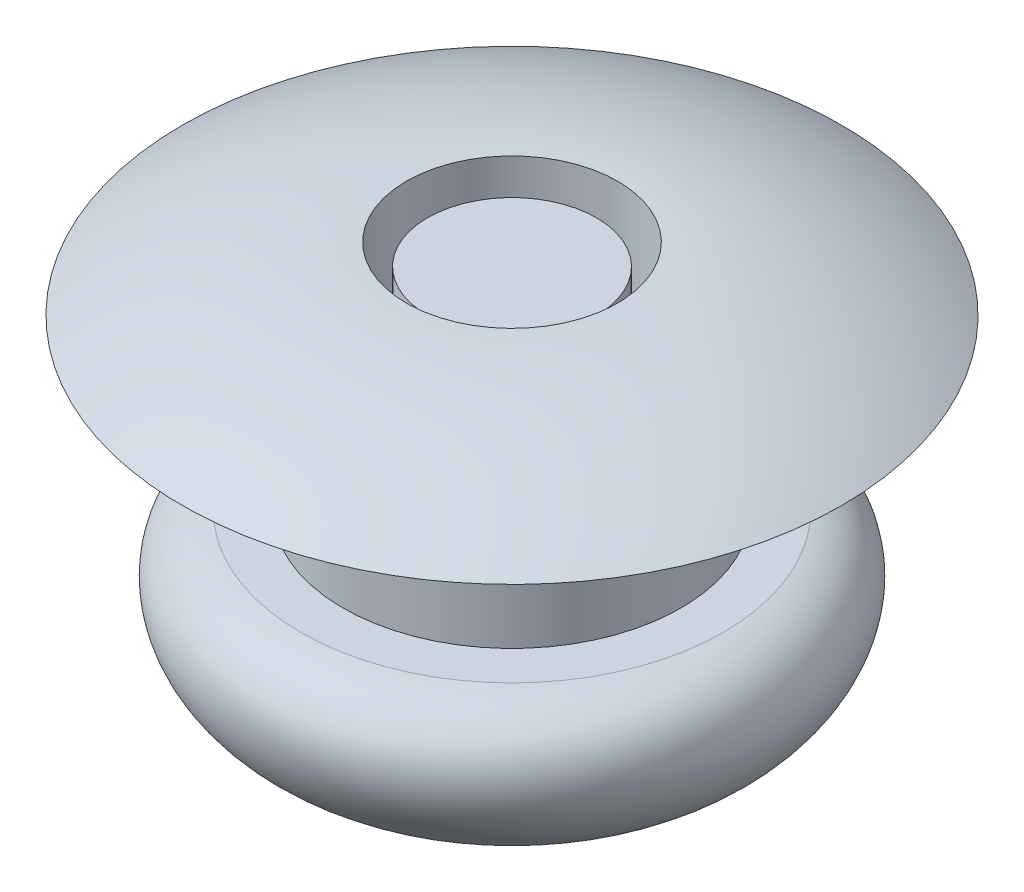
SolidWorks part; units mm, degrees
material "AISI 316 Arkusz stali nierdzewnej (SS)"
ref_plane "Płaszczyzna przednia" through (0, 0, 0) normal (0, 0, 1) x (1, 0, 0)
ref_plane "Płaszczyzna górna" through (0, 0, 0) normal (0, 1, 0) x (1, 0, 0)
ref_plane "Płaszczyzna prawa" through (0, 0, 0) normal (1, 0, 0) x (0, 0, -1)
sketch "Szkic1" plane through (0, 0, 0) normal (0, 0, 1) x (1, 0, 0)
  line L0 (0, 0) -> (0, 0.724) construction
  line L1 (-3.9, 4) -> (-2, 4)
  line L2 (-1.25, 4.75) -> (-1.25, 2)
  line L3 (-2, 4) -> (-2, 2)
  line L4 (-1.25, 2) -> (-1, 2)
  line L5 (-1, 2) -> (-1, 4.5)
  line L6 (-1, 4.5) -> (0, 4.5)
  line L7 (-2, 2) -> (-2.5, 2)
  line L8 (0, 0) -> (0, 0.5785) construction
  line L9 (0, 4.5) -> (0, 0.5785) construction
  line L10 (0, 4.5) -> (0, 0.5785)
  line L11 (3.75, 4) -> (-12.25, 4) construction
  line L15 (8.75, 2) -> (-17.25, 2) construction
  arc A0 (-1.25, 4.75) -> (-3.9, 4) centre (-1.25, -0.3067) ccw
  spline S0 degree 3 poles (-2.5, 2) (-3.3276, 1.8522) (-3.2549, 0.0346) (-0.0301, -0.3768) (-1.229, 1.675) (-0.2169, 0.5088) (0, 0.5785) knots 0 0 0 0 0.343812 0.687239 0.819799 1 1 1 1
  dimension "D1" = 7.8
  dimension "D2" = 0.75
  dimension "D3" = 4
  dimension "D4" = 2.5
  dimension "D5" = 0.5
  dimension "D6" = 2
  dimension "D7" = 5
  dimension "D8" = 1.5978
  dimension "D9" = 0.3519
  dimension "D10" = 1.5835
  dimension "D11" = 1.2582
  dimension "D12" = 1.4215
  dimension "D13" = 0.8591
  dimension "D14" = 0.7171
  dimension "D15" = 1.256
  dimension "D16" = 1.715
  dimension "D17" = 5.1929
  dimension "D18" = 6.0862
revolve "Obrót1" add sketch "Szkic1" angle 360 about L9
